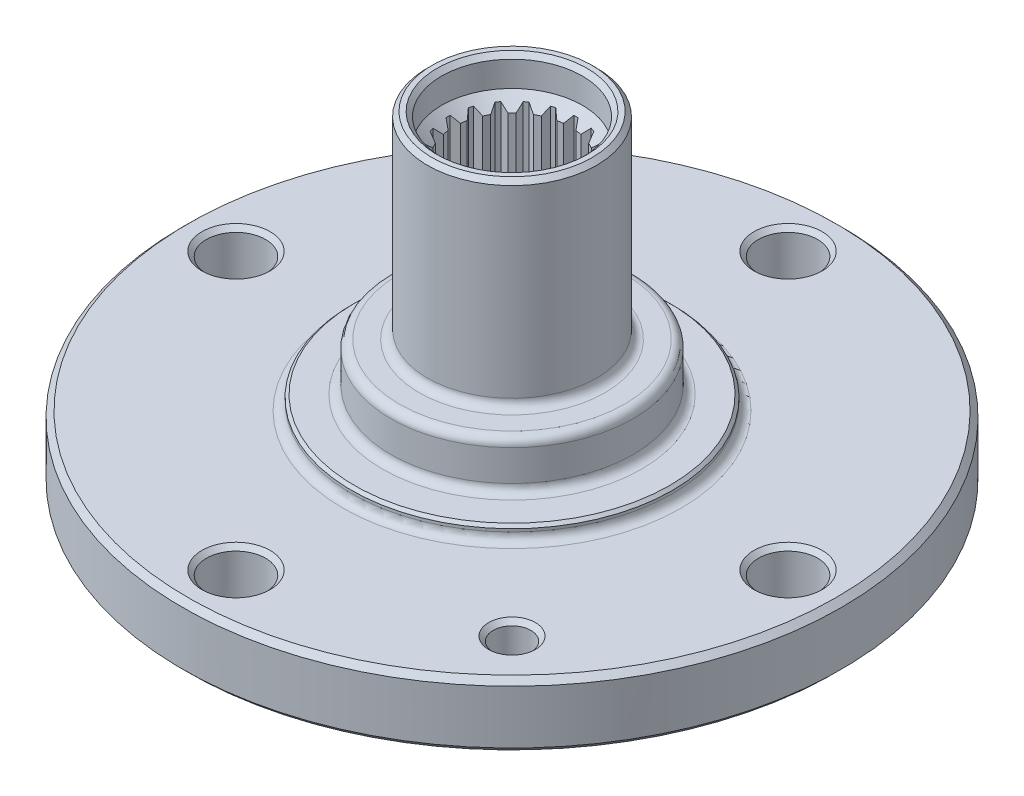
SolidWorks part; units mm, degrees
ref_plane "Front Plane" through (0, 0, 0) normal (0, 0, 1) x (1, 0, 0)
ref_plane "Top Plane" through (0, 0, 0) normal (0, 1, 0) x (1, 0, 0)
ref_plane "Right Plane" through (0, 0, 0) normal (1, 0, 0) x (0, 0, -1)
sketch "Sketch1" plane through (0, 0, 0) normal (0, 0, 1) x (1, 0, 0)
  line L0 (0, 83.796) -> (0, -81.0321) construction
  line L1 (12.5, 68.2923) -> (12.5, 63.2923)
  line L2 (12.5, 63.2923) -> (10.3, 63.2923)
  line L3 (10.3, 63.2923) -> (10.3, 9.7923)
  line L4 (10.3, 9.7923) -> (23.25, 9.7923)
  line L5 (23.25, 9.7923) -> (23.25, -0.2077)
  line L6 (23.25, -0.2077) -> (25.75, -9.2077)
  line L7 (25.75, -9.2077) -> (29, -9.2077)
  line L8 (29, -9.2077) -> (29, 2.2923)
  line L9 (29, 2.2923) -> (29.5, 2.2923)
  line L10 (29.5, 2.2923) -> (29.5, 10.7923)
  line L11 (29.5, 10.7923) -> (58.5, 10.7923)
  line L12 (58.5, 10.7923) -> (58.5, 22.2923)
  line L13 (58.5, 22.2923) -> (28.5, 22.2923)
  line L14 (28.5, 22.2923) -> (28.5, 24.7923)
  line L15 (28.5, 24.7923) -> (21.5, 24.7923)
  line L16 (21.5, 24.7923) -> (21.5, 33.2923)
  line L17 (21.5, 33.2923) -> (15, 33.2923)
  line L18 (15, 33.2923) -> (15, 68.2923)
  line L19 (12.5, 68.2923) -> (15, 68.2923)
  dimension "D2" = 12.5
  dimension "D3" = 15
  dimension "D4" = 21.5
  dimension "D5" = 28.5
  dimension "D6" = 58.5
  dimension "D7" = 23.25
  dimension "D8" = 25.75
  dimension "D9" = 29
  dimension "D10" = 29.5
  dimension "D11" = 9
  dimension "D12" = 19
  dimension "D13" = 20
  dimension "D14" = 8.5
  dimension "D15" = 11.5
  dimension "D16" = 2.5
  dimension "D17" = 8.5
  dimension "D18" = 5
  dimension "D19" = 10.3
  dimension "D20" = 35
revolve "Revolve1" add sketch "Sketch1" angle 360 about L0
chamfer "Chamfer8" distance 2.5 angle 45 1 edges at (-10.3, 63.2923, 0)
sketch "Sketch2" plane through (0, 10.7923, 0) normal (0, -1, 0) x (1, 0, 0)
  circle A1 centre (-49, 0) radius 5.25
  circle A2 centre (-34.6482, -34.6482) radius 3.35
  circle A3 centre (0, 49) radius 5.25
  circle A5 centre (49, 0) radius 5.25
  circle A6 centre (34.6482, 34.6482) radius 3.35
  circle A7 centre (0, -49) radius 5.25
  circle A9 centre (-34.6482, 34.6482) radius 5.25 [skipped]
  circle A10 centre (34.6482, -34.6482) radius 5.25 [skipped]
  circle A11 centre (34.6482, 34.6482) radius 5.25 [skipped]
  circle A12 centre (-34.6482, -34.6482) radius 5.25 [skipped]
  point P21 (0, 0)
  dimension "D1" = 6.7
  dimension "D2" = 10.5
  dimension "D4" = 6.7
  dimension "D3" = 8
extrude "Cut-Extrude1" cut sketch "Sketch2" against normal blind 15
sketch "Sketch3" plane through (0, 9.7923, 0) normal (0, -1, 0) x (1, 0, 0)
  line L0 (-1.25, 10) -> (-0.375, 11.3438)
  line L1 (-1.25, 10) -> (1.25, 10)
  line L2 (0.375, 11.3438) -> (1.25, 10)
  line L3 (1.9013, 9.8968) -> (3.1488, 10.9045)
  line L4 (1.9013, 9.8968) -> (4.279, 9.1243)
  line L5 (3.8621, 10.6727) -> (4.279, 9.1243)
  line L6 (4.8666, 8.8249) -> (6.3643, 9.3977)
  line L7 (4.8666, 8.8249) -> (6.8891, 7.3554)
  line L8 (6.9711, 8.9569) -> (6.8891, 7.3554)
  line L9 (7.3554, 6.8891) -> (8.9569, 6.9711)
  line L10 (7.3554, 6.8891) -> (8.8249, 4.8666)
  line L11 (9.3977, 6.3643) -> (8.8249, 4.8666)
  line L12 (9.1243, 4.279) -> (10.6727, 3.8621)
  line L13 (9.1243, 4.279) -> (9.8968, 1.9013)
  line L14 (10.9045, 3.1488) -> (9.8968, 1.9013)
  line L15 (10, 1.25) -> (11.3438, 0.375)
  line L16 (10, 1.25) -> (10, -1.25)
  line L17 (11.3438, -0.375) -> (10, -1.25)
  line L18 (9.8968, -1.9013) -> (10.9045, -3.1488)
  line L19 (9.8968, -1.9013) -> (9.1243, -4.279)
  line L20 (10.6727, -3.8621) -> (9.1243, -4.279)
  line L21 (8.8249, -4.8666) -> (9.3977, -6.3643)
  line L22 (8.8249, -4.8666) -> (7.3554, -6.8891)
  line L23 (8.9569, -6.9711) -> (7.3554, -6.8891)
  line L24 (6.8891, -7.3554) -> (6.9711, -8.9569)
  line L25 (6.8891, -7.3554) -> (4.8666, -8.8249)
  line L26 (6.3643, -9.3977) -> (4.8666, -8.8249)
  line L27 (4.279, -9.1243) -> (3.8621, -10.6727)
  line L28 (4.279, -9.1243) -> (1.9013, -9.8968)
  line L29 (3.1488, -10.9045) -> (1.9013, -9.8968)
  line L30 (1.25, -10) -> (0.375, -11.3438)
  line L31 (1.25, -10) -> (-1.25, -10)
  line L32 (-0.375, -11.3438) -> (-1.25, -10)
  line L33 (-1.9013, -9.8968) -> (-3.1488, -10.9045)
  line L34 (-1.9013, -9.8968) -> (-4.279, -9.1243)
  line L35 (-3.8621, -10.6727) -> (-4.279, -9.1243)
  line L36 (-4.8666, -8.8249) -> (-6.3643, -9.3977)
  line L37 (-4.8666, -8.8249) -> (-6.8891, -7.3554)
  line L38 (-6.9711, -8.9569) -> (-6.8891, -7.3554)
  line L39 (-7.3554, -6.8891) -> (-8.9569, -6.9711)
  line L40 (-7.3554, -6.8891) -> (-8.8249, -4.8666)
  line L41 (-9.3977, -6.3643) -> (-8.8249, -4.8666)
  line L42 (-9.1243, -4.279) -> (-10.6727, -3.8621)
  line L43 (-9.1243, -4.279) -> (-9.8968, -1.9013)
  line L44 (-10.9045, -3.1488) -> (-9.8968, -1.9013)
  line L45 (-10, -1.25) -> (-11.3438, -0.375)
  line L46 (-10, -1.25) -> (-10, 1.25)
  line L47 (-11.3438, 0.375) -> (-10, 1.25)
  line L48 (-9.8968, 1.9013) -> (-10.9045, 3.1488)
  line L49 (-9.8968, 1.9013) -> (-9.1243, 4.279)
  line L50 (-10.6727, 3.8621) -> (-9.1243, 4.279)
  line L51 (-8.8249, 4.8666) -> (-9.3977, 6.3643)
  line L52 (-8.8249, 4.8666) -> (-7.3554, 6.8891)
  line L53 (-8.9569, 6.9711) -> (-7.3554, 6.8891)
  line L54 (-6.8891, 7.3554) -> (-6.9711, 8.9569)
  line L55 (-6.8891, 7.3554) -> (-4.8666, 8.8249)
  line L56 (-6.3643, 9.3977) -> (-4.8666, 8.8249)
  line L57 (-4.279, 9.1243) -> (-3.8621, 10.6727)
  line L58 (-4.279, 9.1243) -> (-1.9013, 9.8968)
  line L59 (-3.1488, 10.9045) -> (-1.9013, 9.8968)
  line L60 (-1.25, 10) -> (-0.375, 11.3438)
  line L61 (-1.25, 10) -> (1.25, 10)
  line L62 (0.375, 11.3438) -> (1.25, 10)
  arc A0 (3.8621, 10.6727) -> (3.1488, 10.9045) centre (0, 0) ccw
  arc A1 (6.9711, 8.9569) -> (6.3643, 9.3977) centre (0, 0) ccw
  arc A2 (0.375, 11.3438) -> (-0.375, 11.3438) centre (0, 0) ccw
  arc A3 (9.3977, 6.3643) -> (8.9569, 6.9711) centre (0, 0) ccw
  arc A4 (10.9045, 3.1488) -> (10.6727, 3.8621) centre (0, 0) ccw
  arc A5 (11.3438, -0.375) -> (11.3438, 0.375) centre (0, 0) ccw
  arc A6 (10.6727, -3.8621) -> (10.9045, -3.1488) centre (0, 0) ccw
  arc A7 (8.9569, -6.9711) -> (9.3977, -6.3643) centre (0, 0) ccw
  arc A8 (6.3643, -9.3977) -> (6.9711, -8.9569) centre (0, 0) ccw
  arc A9 (3.1488, -10.9045) -> (3.8621, -10.6727) centre (0, 0) ccw
  arc A10 (-0.375, -11.3438) -> (0.375, -11.3438) centre (0, 0) ccw
  arc A11 (-3.8621, -10.6727) -> (-3.1488, -10.9045) centre (0, 0) ccw
  arc A12 (-6.9711, -8.9569) -> (-6.3643, -9.3977) centre (0, 0) ccw
  arc A13 (-9.3977, -6.3643) -> (-8.9569, -6.9711) centre (0, 0) ccw
  arc A14 (-10.9045, -3.1488) -> (-10.6727, -3.8621) centre (0, 0) ccw
  arc A15 (-11.3438, 0.375) -> (-11.3438, -0.375) centre (0, 0) ccw
  arc A16 (-10.6727, 3.8621) -> (-10.9045, 3.1488) centre (0, 0) ccw
  arc A17 (-8.9569, 6.9711) -> (-9.3977, 6.3643) centre (0, 0) ccw
  arc A18 (-6.3643, 9.3977) -> (-6.9711, 8.9569) centre (0, 0) ccw
  arc A19 (-3.1488, 10.9045) -> (-3.8621, 10.6727) centre (0, 0) ccw
  arc A20 (0.375, 11.3438) -> (-0.375, 11.3438) centre (0, 0) ccw
  point P90 (0, 0)
  circle M2 centre (0, 0) radius 10.3
  dimension "D1" = 21
extrude "Cut-Extrude2" cut sketch "Sketch3" against normal blind 100 contours L59 A19 L57 M2 | L2 A2 L0 M2 | L5 A0 L3 M2 | L8 A1 L6 M2 | L11 A3 L9 M2 | L14 A4 L12 M2 | L17 A5 L15 M2 | L20 A6 L18 M2 | L23 A7 L21 M2 | L26 A8 L24 M2 | L29 A9 L27 M2 | L32 A10 L30 M2 | L35 A11 L33 M2 | L38 A12 L36 M2 | L50 A16 L48 M2 | L53 A17 L51 M2 | L56 A18 L54 M2 | L41 L40 L39 A13 | L44 L43 L42 A14 | L47 L46 L45 A15 region at (0, 9.7923, 10.7285) region at (-3.3153, 9.7923, 10.2034) region at (3.3153, 9.7923, 10.2034) region at (-6.3061, 9.7923, 8.6795) region at (6.3061, 9.7923, 8.6795) region at (-8.6795, 9.7923, 6.3061) region at (8.6795, 9.7923, 6.3061) region at (-10.2034, 9.7923, 3.3153) region at (10.2034, 9.7923, 3.3153) region at (10.7285, 9.7923, 0) region at (10.2034, 9.7923, -3.3153) region at (8.6795, 9.7923, -6.3061) region at (-6.3061, 9.7923, -8.6795) region at (6.3061, 9.7923, -8.6795) region at (-3.3153, 9.7923, -10.2034) region at (3.3153, 9.7923, -10.2034) region at (0, 9.7923, -10.7285)
chamfer "Chamfer1" distance 0.8 angle 45 12 edges at (5.25, 22.2923, 49) (5.25, 10.7923, 49) (37.9982, 22.2923, 34.6482) (37.9982, 10.7923, 34.6482) (54.25, 22.2923, 0) (54.25, 10.7923, 0) (5.25, 22.2923, -49) (5.25, 10.7923, -49) (-31.2982, 22.2923, -34.6482) (-31.2982, 10.7923, -34.6482) (-43.75, 22.2923, 0) (-43.75, 10.7923, 0)
chamfer "Chamfer2" distance 1 angle 45 2 edges at (-58.5, 22.2923, 0) (-58.5, 10.7923, 0)
fillet "Fillet1" radius 1.5 1 edges at (-29.5, 10.7923, 0)
chamfer "Chamfer3" distance 1 angle 45 1 edges at (-23.25, 9.7923, 0)
chamfer "Chamfer4" distance 0.8 angle 45 2 edges at (-25.75, -9.2077, 0) (-29, -9.2077, 0) first distance on face at (-25.75, -9.2077, 0) first distance on face at (-29, -9.2077, 0)
fillet "Fillet2" radius 0.5 1 edges at (-29.5, 2.2923, 0)
fillet "Fillet3" radius 1.5 1 edges at (-28.5, 22.2923, 0)
chamfer "Chamfer5" distance 0.5 angle 45 1 edges at (-28.5, 24.7923, 0)
fillet "Fillet4" radius 1.5 3 edges at (-15, 33.2923, 0) (-21.5, 33.2923, 0) (-21.5, 24.7923, 0)
chamfer "Chamfer6" distance 0.8 angle 45 2 edges at (-12.5, 68.2923, 0) (-15, 68.2923, 0)
